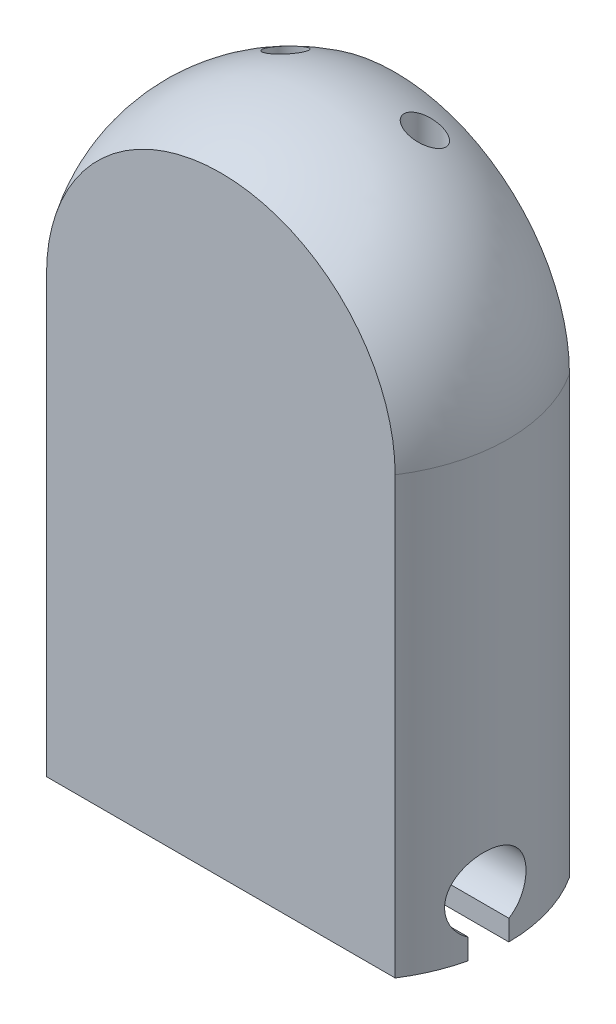
SolidWorks part; units mm, degrees
ref_plane "Front Plane" through (0, 0, 0) normal (0, 0, 1) x (1, 0, 0)
ref_plane "Top Plane" through (0, 0, 0) normal (0, 1, 0) x (1, 0, 0)
ref_plane "Right Plane" through (0, 0, 0) normal (1, 0, 0) x (0, 0, -1)
sketch "Sketch1" plane through (0, 0, 0) normal (0, 0, 1) x (1, 0, 0)
  line L0 (10, 0) -> (-10, 0)
  line L1 (0, 41.8397) -> (0, -28.0151) construction
  line L2 (-10, 0) -> (-10, 25)
  line L4 (10, 25) -> (10, 0)
  arc A0 (10, 25) -> (-10, 25) centre (0, 25) ccw
  point P6 (0, 0)
  dimension "D4" = 10
  dimension "D1" = 10
  dimension "D3" = 25
extrude "Boss-Extrude1" add sketch "Sketch1" along normal blind 10
sketch "Sketch16" plane through (0, 0, 0) normal (0, -1, 0) x (1, 0, 0)
  line L0 (-10, 0) -> (-10, 10)
  line L1 (0, 0) -> (0, 4.5868) construction
  line L2 (10, 0) -> (10, 10)
  arc A0 (-10, 0) -> (-10, 10) centre (-2.2447, 5) cw
  arc A1 (10, 0) -> (10, 10) centre (2.2447, 5) ccw
extrude "Boss-Extrude2" add sketch "Sketch16" against normal blind 25
sketch "Sketch18" plane through (0, 25, 0) normal (0, 1, 0) x (1, 0, 0)
  line L0 (10, -10) -> (10, 0)
  line L1 (10, 0) -> (9.9455, 0.0103)
  line L2 (0, 0) -> (0, -3.5485) construction
  arc A0 (10, 0) -> (10, -10) centre (2.2447, -5) cw
revolve "Revolve1" add sketch "Sketch18" angle 360 about L2 region at (10.5931, 25, 5)
sketch "Sketch11" plane through (0, 0, 0) normal (0, -1, 0) x (1, 0, 0)
  line L0 (-10, 10) -> (-10, 0) construction
  line L1 (-10, 0) -> (10, 0) construction
  line L4 (-10, 2.2959) -> (-10, 4.5918)
  line L5 (8.1, 2.2959) -> (-8.6978, 2.2959) construction
  line L6 (0, 0) -> (0, 6.168) construction
  circle A0 centre (4, 2.2959) radius 1
  circle A1 centre (-4, 2.2959) radius 1
  dimension "D2" = 2
  dimension "D1" = 4
  dimension "D3" = 2.2959
extrude "Cut-Extrude9" cut sketch "Sketch11" against normal through all contours A0 | A1 region at (4, 0, 2.2959) region at (-4, 0, 2.2959)
sketch "Sketch14" plane through (0, 0, 0) normal (-1, 0, 0) x (0, 0, 1)
  line L0 (4.95, 0) -> (7.05, 0)
  line L1 (10, 0) -> (0, 0) construction
  line L2 (6, 3) -> (6, -2.0344) construction
  line L3 (7.05, 0) -> (7.05, 1.1813)
  line L4 (10, 25) -> (10, 0) construction
  line L5 (4.95, 0) -> (4.95, 1.1813)
  circle A0 centre (6, 3) radius 2.1
  point P10 (6, 0)
  dimension "D1" = 4.2
  dimension "D2" = 4
  dimension "D3" = 3
  dimension "D4" = 1.05
extrude "Cut-Extrude16" cut sketch "Sketch14" against normal blind 14.1 and the other way blind 14.1 contours A0 | A0 | A0 L2 L0 L3 region at (0, 0.499, 5.4505) region at (0, 0.499, 6.5495) region at (0, 4.7672, 4.9797)
sketch "Sketch17" plane through (0, 0, 0) normal (0, 0, -1) x (-1, 0, 0)
  line L0 (11.4721, 25) -> (-11.4721, 25)
  arc A0 (-11.4721, 25) -> (11.4721, 25) centre (0, 23.4196) cw
